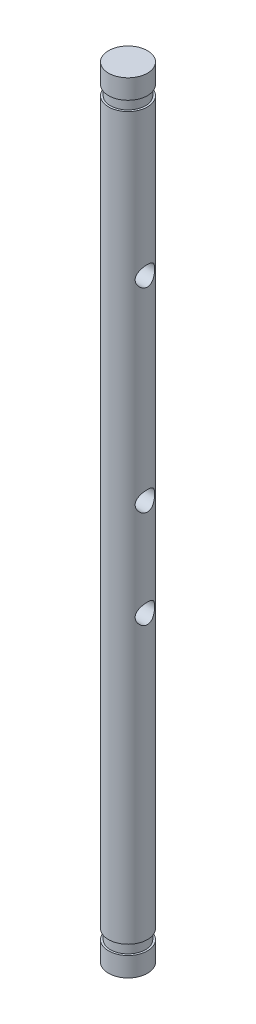
SolidWorks part; units mm, degrees
ref_plane "Alzado" through (0, 0, 0) normal (0, 0, 1) x (1, 0, 0)
ref_plane "Planta" through (0, 0, 0) normal (0, 1, 0) x (1, 0, 0)
ref_plane "Vista lateral" through (0, 0, 0) normal (1, 0, 0) x (0, 0, -1)
sketch "Croquis1" plane through (0, 0, 0) normal (0, 1, 0) x (1, 0, 0)
  circle A0 centre (0, 0) radius 2
  dimension "D1" = 4
extrude "Saliente-Extruir1" add sketch "Croquis1" along normal blind 80
ref_axis "Eje1" through (0, 80, 0) along (0, -1, 0)
sketch "Croquis2" plane through (0, 0, 0) normal (0, 0, 1) x (1, 0, 0)
  line L0 (2, 0) -> (2, 80) construction
  line L1 (1.8, 78) -> (8.3312, 78)
  line L2 (1.8, 78) -> (1.8, 77)
  line L3 (1.8, 77) -> (8.3312, 77)
  line L4 (8.3312, 78) -> (8.3312, 77)
  line L5 (2, 80) -> (-2, 80) construction
  line L6 (-2, 0) -> (2, 0) construction
  line L7 (1.8, 3) -> (8.3312, 3)
  line L8 (1.8, 3) -> (1.8, 2)
  line L9 (1.8, 2) -> (8.3312, 2)
  line L10 (8.3312, 3) -> (8.3312, 2)
  line L11 (2, 0) -> (2, 80) construction
  dimension "D1" = 1
  dimension "D2" = 0.2
  dimension "D3" = 2
  dimension "D4" = 2
  dimension "D5" = 0.2
revolve "Cortar-Revolución1" cut sketch "Croquis2" angle 360 about axis through (0, 80, 0) along (0, -1, 0)
sketch "Croquis3" plane through (0, 0, 0) normal (1, 0, 0) x (0, 0, -1)
  line L0 (0, 80) -> (0, 0) construction
  line L2 (2, 80) -> (-2, 80) construction
  circle A0 centre (0, 42) radius 1
  circle A1 centre (0, 32) radius 1
  circle A2 centre (0, 62) radius 1
  dimension "D1" = 2
  dimension "D2" = 10
  dimension "D3" = 20
  dimension "D5" = 2
  dimension "D4" = 18
extrude "Cortar-Extruir1" cut sketch "Croquis3" against normal through all both and the other way through all
